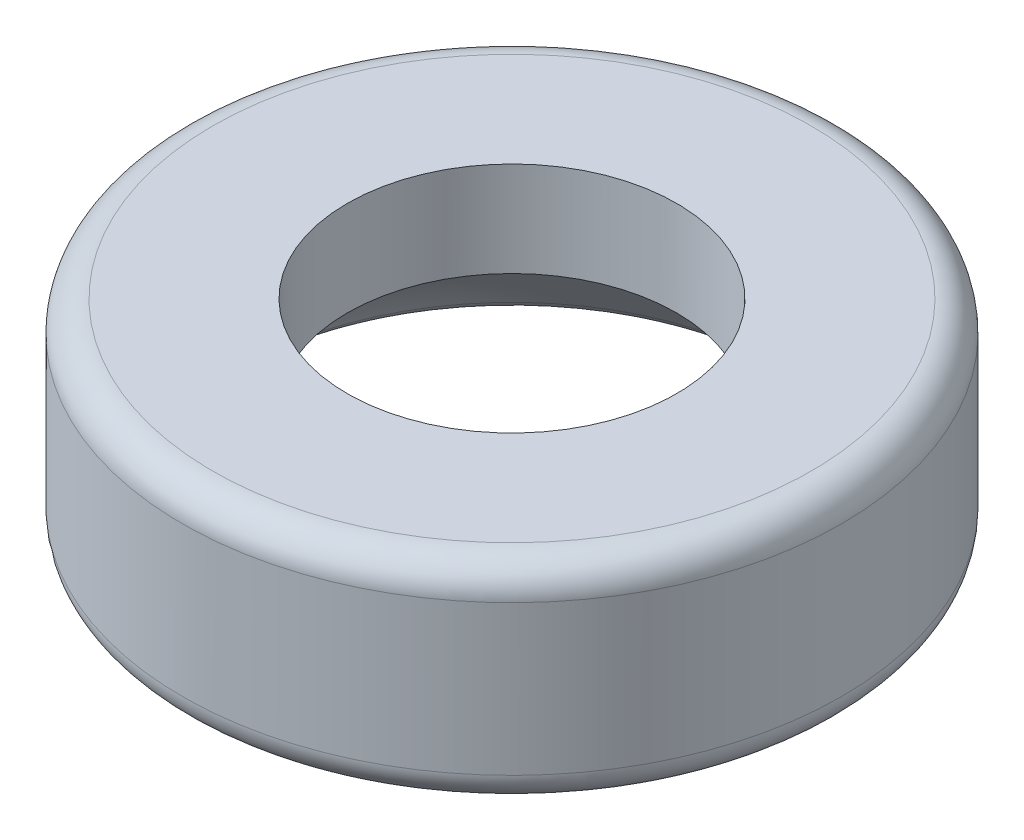
SolidWorks part; units mm, degrees
ref_plane "Front Plane" through (0, 0, 0) normal (0, 0, 1) x (1, 0, 0)
ref_plane "Top Plane" through (0, 0, 0) normal (0, 1, 0) x (1, 0, 0)
ref_plane "Right Plane" through (0, 0, 0) normal (1, 0, 0) x (0, 0, -1)
sketch "Sketch1" plane through (0, 0, 0) normal (0, 0, 1) x (1, 0, 0)
  line L0 (-45.5232, 0) -> (2227.6011, 0) construction
  line L1 (0, -45.4625) -> (0, 2227.6618) construction
  line L2 (0, 4.1275) -> (0, 4.7625)
  line L3 (0, 4.7625) -> (4.1275, 4.7625)
  line L4 (4.1275, 4.7625) -> (4.1275, 0)
  arc A0 (0, 4.1275) -> (4.1275, 0) centre (0, 0) cw
  dimension "D2" = 4.1275
  dimension "D1" = 4.1275
  dimension "D3" = 4.7625
revolve "Revolve1" add sketch "Sketch1" angle 360 about L1
fillet "Fillet1" radius 0.381 2 edges at (4.1275, 4.7625, 0) (4.1275, 0, 0)
sketch "Sketch2" plane through (0, 4.7625, 0) normal (0, 1, 0) x (1, 0, 0)
  circle A0 centre (0, 0) radius 2.0638
  dimension "D1" = 4.1275
extrude "Cut-Extrude1" cut sketch "Sketch2" against normal through all
